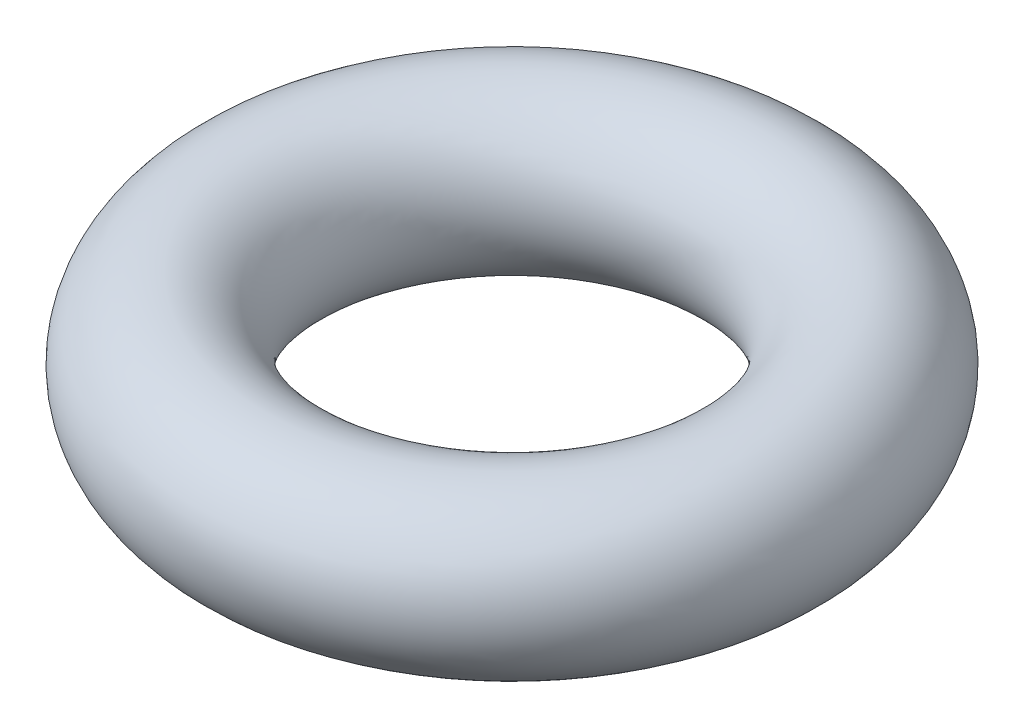
SolidWorks part; units mm, degrees
ref_plane "Front Plane" through (0, 0, 0) normal (0, 0, 1) x (1, 0, 0)
ref_plane "Top Plane" through (0, 0, 0) normal (0, 1, 0) x (1, 0, 0)
ref_plane "Right Plane" through (0, 0, 0) normal (1, 0, 0) x (0, 0, -1)
sketch "Sketch1" plane through (0, 0, 0) normal (0, 0, 1) x (1, 0, 0)
  line L0 (-1.8415, 0) -> (1.8415, 0) construction
  line L1 (-3.6195, 0) -> (3.6195, 0) construction
  circle A0 centre (-2.7305, 0) radius 0.889 construction
  dimension "Width" = 1.778
  dimension "ID" = 3.683
  dimension "OD" = 7.239
sketch "Sketch3" plane through (0, 0, 0) normal (1, 0, 0) x (0, 0, -1)
  line L0 (0, 0) -> (-1.2277, 0) construction
  line L1 (-1.2277, 0) -> (-1.2277, 0.889) construction
  point P0 (-1.2277, 0.889)
  dimension "D1" = 1.2277
  dimension "D2" = 0.889
sketch "Sketch2" plane through (0, 0, 0) normal (0, 0, 1) x (1, 0, 0)
  line L0 (0, 0) -> (0, 0.889) construction
  line L1 (-1.8415, 0) -> (1.8415, 0) construction
  circle A0 centre (-2.7305, 0) radius 0.889 construction
  circle A1 centre (-2.7305, 0) radius 0.889
  point P7 (-2.7305, 0.889)
revolve "Revolve1" add sketch "Sketch2" angle 360 about L0
ref_axis "Center Axis 1" through (0, 0.9779, 0) along (0, -1, 0)
sketch "Sketch4" plane through (0, 0, 0) normal (0, 1, 0) x (1, 0, 0)
  circle A0 centre (0, 0) radius 1.617
  dimension "D1" = 3.2339
equation "\"D1@Sketch3\"=\"ID@Sketch1\"/3"
equation "\"D2@Sketch3\"=\"Width@Sketch1\"/2"
